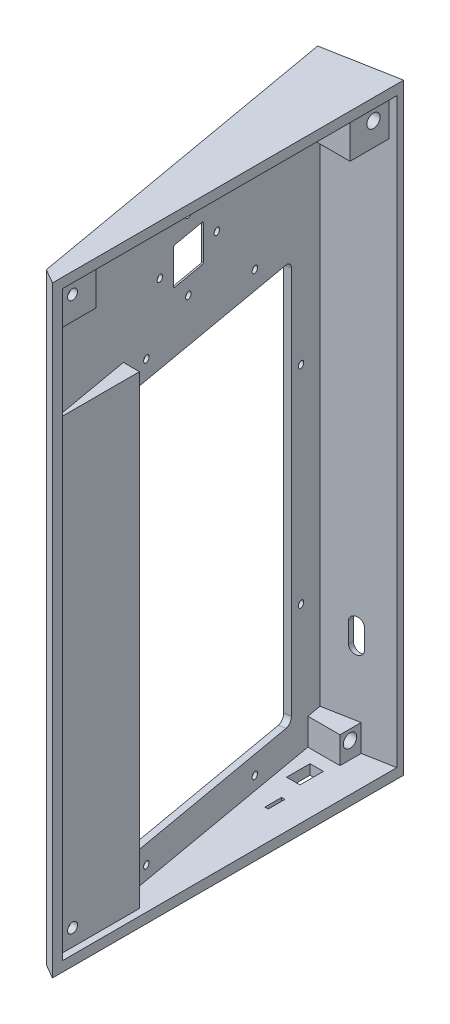
SolidWorks part; units mm, degrees
ref_plane "前视基准面" through (0, 0, 0) normal (0, 0, 1) x (1, 0, 0)
ref_plane "上视基准面" through (0, 0, 0) normal (0, 1, 0) x (1, 0, 0)
ref_plane "右视基准面" through (0, 0, 0) normal (1, 0, 0) x (0, 0, -1)
other "Configuration Table"
sketch "草图1" plane through (0, 0, 0) normal (0, 1, 0) x (1, 0, 0)
  line L0 (82.9035, -37.3993) -> (82.9035, -142.3993)
  line L1 (82.9035, -142.3993) -> (78.5734, -139.8993)
  line L2 (78.5734, -139.8993) -> (61.2086, -41.4185)
  line L3 (61.2086, -41.4185) -> (82.9035, -37.3993)
  dimension "D1" = 100
  dimension "D2" = 105
  dimension "D3" = 5
  dimension "D4" = 170
  dimension "D5" = 60
  dimension "D6" = 90.496
  dimension "D7" = 79.504
extrude "凸台-拉伸1" add sketch "草图1" along normal blind 180
sketch "草图5" plane through (52.2799, 0, -9.2184) normal (-0.9848, 0, 0.1736) x (0.1736, 0, 0.9848)
  line L0 (51.418, 180) -> (51.418, 0) construction
  line L1 (138.918, 12.5) -> (63.918, 12.5)
  line L2 (138.918, 12.5) -> (138.918, 132.5)
  line L3 (138.918, 132.5) -> (63.918, 132.5)
  line L4 (63.918, 12.5) -> (63.918, 132.5)
  line L5 (151.418, 180) -> (151.418, 0) construction
  line L6 (51.418, 0) -> (151.418, 0) construction
  dimension "D1" = 75
  dimension "D2" = 120
  dimension "D3" = 12.5
  dimension "D4" = 12.5
  dimension "D5" = 12.5
extrude "切除-拉伸2" cut sketch "草图5" against normal blind 2
sketch "草图7" plane through (82.9035, 0, 0) normal (1, 0, 0) x (0, 0, -1)
  line L8 (-139.3993, 3) -> (-40.3993, 3)
  line L9 (-40.3993, 3) -> (-40.3993, 177)
  line L10 (-40.3993, 177) -> (-139.3993, 177)
  line L11 (-139.3993, 177) -> (-139.3993, 3)
  line L12 (-139.3993, 3) -> (-40.3993, 3)
  line L13 (-40.3993, 3) -> (-40.3993, 177)
  line L14 (-40.3993, 177) -> (-139.3993, 177)
  line L15 (-139.3993, 177) -> (-139.3993, 3)
  dimension "D1" = 3
extrude "切除-拉伸3" cut sketch "草图7" against normal up to surface (19.8438 mm away) up to face at (71.8606, 72.5, 90.3116)
sketch "草图10" plane through (54.2496, 0, -9.5657) normal (0.9848, 0, -0.1736) x (-0.1736, 0, -0.9848)
  line L1 (-63.918, 12.5) -> (-60.418, 12.5) construction
  line L2 (-63.918, 12.5) -> (-63.918, 41.5) construction
  line L3 (-63.918, 41.5) -> (-60.418, 41.5) construction
  line L4 (-60.418, 12.5) -> (-60.418, 41.5) construction
  line L5 (-63.918, 132.5) -> (-60.418, 132.5) construction
  line L6 (-63.918, 132.5) -> (-63.918, 103.5) construction
  line L7 (-63.918, 103.5) -> (-60.418, 103.5) construction
  line L8 (-60.418, 132.5) -> (-60.418, 103.5) construction
  circle A0 centre (-60.418, 103.5) radius 1
  circle A1 centre (-60.418, 41.5) radius 1
  dimension "D1" = 29
  dimension "D2" = 29
  dimension "D3" = 3.5
  dimension "D4" = 3.5
extrude "切除-拉伸5" cut sketch "草图10" against normal blind 1
sketch "草图11" plane through (54.2496, 0, -9.5657) normal (0.9848, 0, -0.1736) x (-0.1736, 0, -0.9848)
  line L0 (-77.418, 7) -> (-117.418, 7) construction
  line L1 (-63.918, 132.5) -> (-77.418, 132.5) construction
  line L2 (-63.918, 132.5) -> (-63.918, 138) construction
  line L3 (-63.918, 138) -> (-77.418, 138) construction
  line L4 (-77.418, 132.5) -> (-77.418, 138) construction
  line L5 (-63.918, 12.5) -> (-77.418, 12.5) construction
  line L6 (-63.918, 12.5) -> (-63.918, 7) construction
  line L7 (-63.918, 7) -> (-77.418, 7) construction
  line L8 (-77.418, 12.5) -> (-77.418, 7) construction
  line L9 (-77.418, 138) -> (-117.418, 138) construction
  circle A0 centre (-117.418, 138) radius 1
  circle A1 centre (-77.418, 138) radius 1
  circle A2 centre (-117.418, 7) radius 1
  circle A3 centre (-77.418, 7) radius 1
  dimension "D1" = 13.5
  dimension "D2" = 5.5
  dimension "D3" = 13.5
  dimension "D4" = 5.5
  dimension "D5" = 40
  dimension "D6" = 40
extrude "切除-拉伸6" cut sketch "草图11" against normal blind 1
sketch "草图12" plane through (82.9035, 0, 0) normal (1, 0, 0) x (0, 0, -1)
  line L1 (-139.3993, 3) -> (-114.3993, 3)
  line L2 (-139.3993, 3) -> (-139.3993, 142)
  line L3 (-139.3993, 142) -> (-114.3993, 142)
  line L4 (-114.3993, 3) -> (-114.3993, 142)
  line L6 (-127.2419, 132.5) -> (-53.3813, 132.5) construction
  dimension "D1" = 9.5
  dimension "D2" = 25
extrude "凸台-拉伸3" add sketch "草图12" against normal up to surface (2.3874 mm away) up to face at (67.5194, 138, 65.6914)
sketch "草图13" plane through (54.2496, 0, -9.5657) normal (-0.9848, 0, 0.1736) x (0.1736, 0, 0.9848)
  line L4 (125.8773, 12.5) -> (138.918, 12.5)
  line L5 (138.918, 12.5) -> (138.918, 132.5)
  line L6 (138.918, 132.5) -> (125.8773, 132.5)
  line L7 (125.8773, 132.5) -> (125.8773, 12.5)
  line L8 (125.8773, 12.5) -> (138.918, 12.5)
  line L9 (138.918, 12.5) -> (138.918, 132.5)
  line L10 (138.918, 132.5) -> (125.8773, 132.5)
  line L11 (125.8773, 132.5) -> (125.8773, 12.5)
  dimension "D1" = 0
extrude "切除-拉伸7" cut sketch "草图13" against normal blind 2
sketch "草图14" plane through (52.2799, 0, -9.2184) normal (-0.9848, 0, 0.1736) x (0.1736, 0, 0.9848)
  line L0 (51.418, 180) -> (51.418, 0) construction
  line L1 (96.418, 150.5) -> (107.418, 150.5)
  line L2 (96.418, 150.5) -> (96.418, 161.5)
  line L3 (96.418, 161.5) -> (107.418, 161.5)
  line L4 (107.418, 150.5) -> (107.418, 161.5)
  line L5 (138.918, 132.5) -> (63.918, 132.5) construction
  line L6 (51.418, 180) -> (151.418, 180) construction
  dimension "D1" = 11
  dimension "D2" = 11
  dimension "D3" = 45
  dimension "D4" = 18
  dimension "D5" = 18.5
extrude "切除-拉伸8" cut sketch "草图14" against normal blind 2
chamfer "倒角1" distance 1.5 angle 60 4 edges at (70.9329, 156, 96.5677) (69.9778, 150.5, 91.1513) (69.9778, 161.5, 91.1513) (69.0228, 156, 85.7348) first distance on face at (71.9177, 156, 96.3941) first distance on face at (70.9626, 150.5, 90.9776) first distance on face at (70.9626, 161.5, 90.9776) first distance on face at (70.0076, 156, 85.5612)
fillet "圆角2" radius 0.5 4 edges at (72.6563, 150.5, 96.2638) (72.6563, 161.5, 96.2638) (70.7462, 161.5, 85.431) (70.7462, 150.5, 85.431)
sketch "草图17" plane through (9.4497, 0, 51.0074) normal (-0.1822, 0, -0.9833) x (-0.9833, 0, 0.1822)
  line L1 (-74.7037, 180) -> (-52.6396, 180)
  line L2 (-74.7037, 180) -> (-74.7037, 0)
  line L3 (-74.7037, 0) -> (-52.6396, 0)
  line L4 (-52.6396, 180) -> (-52.6396, 0)
extrude "凸台-拉伸9" add sketch "草图17" against normal blind 2
sketch "草图18" plane through (0, 0, 0) normal (0, -1, 0) x (1, 0, 0)
  line L0 (82.9035, 39.4333) -> (82.9035, 37.3993)
  line L1 (83.2679, 39.3658) -> (82.9035, 39.4333) construction
  line L2 (83.2679, 39.3658) -> (82.9035, 37.3993) construction
  line L3 (83.2679, 39.3658) -> (82.9035, 37.3993)
  line L4 (83.2679, 39.3658) -> (82.9035, 39.4333)
extrude "切除-拉伸9" cut sketch "草图18" against normal up to surface (180 mm away) up to face at (78.6267, 180, 73.3192)
sketch "草图19" plane through (0, 3, 0) normal (0, 1, 0) x (1, 0, 0)
  line L0 (82.9035, -40.3993) -> (82.9035, -36.7908) construction
  line L1 (77.596, -40.4166) -> (82.9035, -39.4333)
  line L2 (63.5225, -43.0238) -> (77.6894, -40.3993) construction
  line L3 (82.9035, -39.4333) -> (82.9035, -40.3993)
  line L4 (82.9035, -40.3993) -> (77.596, -40.4166)
extrude "切除-拉伸10" cut sketch "草图19" along normal up to surface (174 mm away) up to face at (77.507, 177, 80.5242)
sketch "草图20" plane through (82.9035, 0, 0) normal (1, 0, 0) x (0, 0, -1)
  line L1 (-139.3993, 142) -> (-114.3993, 142)
  line L2 (-139.3993, 142) -> (-139.3993, 3)
  line L3 (-139.3993, 3) -> (-114.3993, 3)
  line L4 (-114.3993, 142) -> (-114.3993, 3)
extrude "切除-拉伸11" cut sketch "草图20" against normal blind 2
sketch "草图21" plane through (54.2496, 0, -9.5657) normal (0.9848, 0, -0.1736) x (-0.1736, 0, -0.9848)
  line L0 (-107.418, 156) -> (-112.418, 156) construction
  line L1 (-107.418, 151) -> (-107.418, 161) construction
  line L2 (-101.918, 161.5) -> (-101.918, 166.5) construction
  line L3 (-106.918, 161.5) -> (-96.918, 161.5) construction
  line L4 (-96.418, 156) -> (-91.418, 156) construction
  line L5 (-96.418, 161) -> (-96.418, 151) construction
  line L6 (-101.918, 150.5) -> (-101.918, 145.5) construction
  line L7 (-96.918, 150.5) -> (-106.918, 150.5) construction
  circle A0 centre (-112.418, 156) radius 1
  circle A1 centre (-91.418, 156) radius 1
  circle A2 centre (-101.918, 145.5) radius 1
  circle A3 centre (-101.918, 166.5) radius 1
  dimension "D1" = 5
extrude "切除-拉伸12" cut sketch "草图21" against normal blind 1
sketch "草图23" plane through (80.9035, 0, 0) normal (1, 0, 0) x (0, 0, -1)
  line L0 (-51.4333, 8) -> (-51.4333, 26.4031) construction
  line L1 (-139.3993, 3) -> (-127.3993, 3)
  line L2 (-139.3993, 3) -> (-139.3993, 15)
  line L3 (-139.3993, 15) -> (-127.3993, 15)
  line L4 (-127.3993, 3) -> (-127.3993, 15)
  line L5 (-39.4333, 177) -> (-139.3993, 177) construction
  line L11 (-51.4333, 165) -> (-39.4333, 165)
  line L12 (-51.4333, 165) -> (-51.4333, 177)
  line L13 (-51.4333, 177) -> (-39.4333, 177)
  line L14 (-39.4333, 165) -> (-39.4333, 177)
  line L15 (-127.3993, 8) -> (-127.3993, 23.4787) construction
  line L17 (-127.3993, 165) -> (-139.3993, 165)
  line L18 (-127.3993, 165) -> (-127.3993, 177)
  line L19 (-127.3993, 177) -> (-139.3993, 177)
  line L20 (-139.3993, 165) -> (-139.3993, 177)
  dimension "D1" = 12
  dimension "D2" = 12
  dimension "D5" = 0
  dimension "D6" = 12
  dimension "D7" = 12
  dimension "D8" = 12
  dimension "D9" = 12
  dimension "D11" = 0
extrude "凸台-拉伸10" add sketch "草图23" against normal up to surface (0.3874 mm away) up to face at (73.5971, 156, 100.1597)
fillet "圆角4" radius 2 4 edges at (64.364, 132.5, 53.5549) (78.3724, 132.5, 127.2419) (64.364, 12.5, 53.5549) (78.3724, 12.5, 127.2419)
sketch "草图26" plane through (0, 177, 0) normal (0, 1, 0) x (1, 0, 0)
  line L3 (63.1752, -41.0542) -> (71.9242, -39.4333)
  line L4 (71.9242, -39.4333) -> (62.8894, -39.4333)
  line L5 (62.8894, -39.4333) -> (63.1752, -41.0542)
  line L6 (63.1752, -41.0542) -> (71.9242, -39.4333)
  line L7 (71.9242, -39.4333) -> (62.8894, -39.4333)
  line L8 (62.8894, -39.4333) -> (63.1752, -41.0542)
  dimension "D1" = 0
extrude "切除-拉伸15" cut sketch "草图26" against normal up to next
sketch "草图27" plane through (82.9035, 0, 0) normal (1, 0, 0) x (0, 0, -1)
  line L1 (-39.4333, 3) -> (-47.4333, 3)
  line L2 (-39.4333, 3) -> (-39.4333, 11)
  line L3 (-39.4333, 11) -> (-47.4333, 11)
  line L4 (-47.4333, 3) -> (-47.4333, 11)
  dimension "D1" = 8
  dimension "D2" = 8
extrude "凸台-拉伸11" add sketch "草图27" against normal up to surface (18.6035 mm away) up to face at (73.5971, 156, 100.1597)
sketch "草图28" plane through (82.9035, 0, 0) normal (1, 0, 0) x (0, 0, -1)
  line L1 (-47.4333, 3) -> (-39.4333, 3)
  line L2 (-47.4333, 3) -> (-47.4333, 11)
  line L3 (-47.4333, 11) -> (-39.4333, 11)
  line L4 (-39.4333, 3) -> (-39.4333, 11)
extrude "切除-拉伸16" cut sketch "草图28" against normal blind 9
sketch "草图29" plane through (0, 11, 0) normal (0, -1, 0) x (1, 0, 0)
  line L3 (73.9035, 41.1006) -> (73.9035, 39.4333)
  line L4 (73.9035, 39.4333) -> (82.9035, 39.4333)
  line L5 (82.9035, 39.4333) -> (73.9035, 41.1006)
  line L6 (73.9035, 41.1006) -> (73.9035, 39.4333)
  line L7 (73.9035, 39.4333) -> (82.9035, 39.4333)
  line L8 (82.9035, 39.4333) -> (73.9035, 41.1006)
  dimension "D1" = 0
extrude "凸台-拉伸12" add sketch "草图29" along normal up to surface (8 mm away) up to face at (76.9786, 3, 85.1663)
sketch "草图30" plane through (0, 3, 0) normal (0, -1, 0) x (1, 0, 0)
  line L3 (71.9242, 39.4333) -> (63.1752, 41.0542)
  line L4 (63.1752, 41.0542) -> (62.8894, 39.4333)
  line L5 (62.8894, 39.4333) -> (71.9242, 39.4333)
  line L6 (71.9242, 39.4333) -> (63.1752, 41.0542)
  line L7 (63.1752, 41.0542) -> (62.8894, 39.4333)
  line L8 (62.8894, 39.4333) -> (71.9242, 39.4333)
  dimension "D1" = 0
extrude "切除-拉伸17" cut sketch "草图30" against normal up to next
sketch "草图31" plane through (0, 0, 0) normal (0, -1, 0) x (1, 0, 0)
  line L1 (82.9035, 37.3993) -> (68.9035, 37.3993) construction
  line L2 (82.9035, 37.3993) -> (82.9035, 51.3993) construction
  line L3 (82.9035, 51.3993) -> (68.9035, 51.3993) construction
  line L4 (68.9035, 37.3993) -> (68.9035, 51.3993) construction
  line L5 (68.9035, 51.3993) -> (72.9035, 51.3993)
  line L6 (68.9035, 51.3993) -> (68.9035, 58.3993)
  line L7 (68.9035, 58.3993) -> (72.9035, 58.3993)
  line L8 (72.9035, 51.3993) -> (72.9035, 58.3993)
  dimension "D1" = 14
  dimension "D2" = 14
  dimension "D3" = 7
  dimension "D4" = 4
extrude "切除-拉伸18" cut sketch "草图31" against normal up to next
ref_plane "基准面1" through (0, 0, 37.3993) normal (0, 0, -1) x (-1, 0, 0)
ref_plane "基准面2" through (0, 0, 39.7193) normal (0, 0, -1) x (-1, 0, 0)
sketch "草图32" plane through (0, 0, 39.7193) normal (0, 0, -1) x (-1, 0, 0)
  line L0 (-72.7086, 36) -> (-72.7086, 30) construction
  line L1 (-70.7086, 36) -> (-70.7086, 30)
  line L2 (-74.7086, 36) -> (-74.7086, 30)
  line L3 (-82.9035, 180) -> (-61.2086, 180) construction
  line L4 (-61.2086, 180) -> (-61.2086, 0) construction
  arc A0 (-70.7086, 36) -> (-74.7086, 36) centre (-72.7086, 36) ccw
  arc A1 (-74.7086, 30) -> (-70.7086, 30) centre (-72.7086, 30) ccw
  point P2 (-72.7086, 33)
  point P9 (-72.7086, 28)
  point P10 (-72.7086, 38)
  dimension "D1" = 147
  dimension "D2" = 10
  dimension "D3" = 4
  dimension "D4" = 9.5
extrude "切除-拉伸23" cut sketch "草图32" against normal up to surface (1.9733 mm away) up to face at (75.3083, 89, 40.8404)
ref_plane "基准面4" through (0, 0, 40.2193) normal (0, 0, -1) x (-1, 0, 0)
sketch "草图35" plane through (0, 0, 40.2193) normal (0, 0, -1) x (-1, 0, 0)
  line L0 (-74.7086, 36) -> (-74.7086, 30) construction
  line L1 (-76.7086, 41) -> (-68.7086, 41)
  line L2 (-76.7086, 41) -> (-76.7086, 25)
  line L3 (-76.7086, 25) -> (-68.7086, 25)
  line L4 (-68.7086, 41) -> (-68.7086, 25)
  line L5 (-70.7086, 30) -> (-70.7086, 36) construction
  arc A0 (-70.7086, 36) -> (-74.7086, 36) centre (-72.7086, 36) ccw construction
  arc A1 (-74.7086, 30) -> (-70.7086, 30) centre (-72.7086, 30) ccw construction
  dimension "D1" = 5
  dimension "D2" = 5
  dimension "D3" = 2
  dimension "D4" = 2
extrude "切除-拉伸25" cut sketch "草图35" along normal up to surface (0.1902 mm away) up to face at (72.0561, 90, 39.4089)
fillet "圆角5" radius 0.5 4 edges at (76.7086, 25, 39.3831) (76.7086, 41, 39.3831) (68.7086, 25, 40.1241) (68.7086, 41, 40.1241)
sketch "草图36" plane through (0, 0, 0) normal (0, -1, 0) x (1, 0, 0)
  line L1 (82.9035, 37.3993) -> (74.4035, 37.3993) construction
  line L2 (82.9035, 37.3993) -> (82.9035, 64.3993) construction
  line L3 (82.9035, 64.3993) -> (74.4035, 64.3993) construction
  line L4 (74.4035, 37.3993) -> (74.4035, 64.3993) construction
  line L5 (74.4035, 64.3993) -> (73.4035, 64.3993)
  line L6 (74.4035, 64.3993) -> (74.4035, 69.3993)
  line L7 (74.4035, 69.3993) -> (73.4035, 69.3993)
  line L8 (73.4035, 64.3993) -> (73.4035, 69.3993)
  dimension "D1" = 8.5
  dimension "D2" = 27
  dimension "D3" = 1
  dimension "D4" = 5
extrude "切除-拉伸26" cut sketch "草图36" against normal up to next
sketch "草图37" plane through (0, 0, 0) normal (0, -1, 0) x (1, 0, 0)
  line L0 (73.4035, 66.8993) -> (74.4035, 66.8993) construction
  line L1 (73.4035, 69.3993) -> (73.4035, 64.3993) construction
  line L2 (74.4035, 64.3993) -> (74.4035, 69.3993) construction
  line L3 (73.9035, 64.3993) -> (73.9035, 69.3993) construction
  line L4 (73.4035, 64.3993) -> (74.4035, 64.3993) construction
  line L5 (74.4035, 69.3993) -> (73.4035, 69.3993) construction
  line L7 (74.9035, 69.8993) -> (72.9035, 69.8993)
  line L8 (74.9035, 69.8993) -> (74.9035, 63.8993)
  line L9 (74.9035, 63.8993) -> (72.9035, 63.8993)
  line L10 (72.9035, 69.8993) -> (72.9035, 63.8993)
  line L11 (74.9035, 69.8993) -> (72.9035, 63.8993) construction
  line L12 (74.9035, 63.8993) -> (72.9035, 69.8993) construction
  point P12 (73.9035, 66.8993)
  dimension "D1" = 6
  dimension "D2" = 2
extrude "切除-拉伸27" cut sketch "草图37" against normal blind 1
sketch "草图38" plane through (73.9035, 0, 0) normal (1, 0, 0) x (0, 0, -1)
  line L1 (-47.4333, 11) -> (-44.4333, 11) construction
  line L2 (-47.4333, 11) -> (-47.4333, 8) construction
  line L3 (-47.4333, 8) -> (-44.4333, 8) construction
  line L4 (-44.4333, 11) -> (-44.4333, 8) construction
  circle A0 centre (-44.4333, 8) radius 2
  dimension "D1" = 3
  dimension "D2" = 3
extrude "切除-拉伸28" cut sketch "草图38" against normal blind 3 contours A0
sketch "草图39" plane through (80.9035, 0, 0) normal (1, 0, 0) x (0, 0, -1)
  line L0 (-47.4333, 10.1358) -> (-47.4333, 2.8866) construction
  line L4 (-39.8038, 177) -> (-51.4333, 177) construction
  line L5 (-47.4333, 169) -> (-39.8038, 169) construction
  line L6 (-47.4333, 169) -> (-47.4333, 177) construction
  line L7 (-47.4333, 177) -> (-39.8038, 177) construction
  line L8 (-39.8038, 169) -> (-39.8038, 177) construction
  line L10 (-47.4333, 169) -> (-44.4333, 169) construction
  line L11 (-47.4333, 169) -> (-47.4333, 172) construction
  line L12 (-47.4333, 172) -> (-44.4333, 172) construction
  line L13 (-44.4333, 169) -> (-44.4333, 172) construction
  circle A0 centre (-44.4333, 172) radius 2
  dimension "D1" = 8
  dimension "D2" = 3
  dimension "D3" = 3
extrude "切除-拉伸30" cut sketch "草图39" against normal blind 3
sketch "草图40" plane through (80.9035, 0, 0) normal (1, 0, 0) x (0, 0, -1)
  line L1 (-127.3993, 177) -> (-131.3993, 177) construction
  line L2 (-127.3993, 177) -> (-127.3993, 171) construction
  line L3 (-127.3993, 171) -> (-131.3993, 171) construction
  line L4 (-131.3993, 177) -> (-131.3993, 171) construction
  line L5 (-131.3993, 171) -> (-134.3993, 171) construction
  line L6 (-131.3993, 171) -> (-131.3993, 172) construction
  line L7 (-131.3993, 172) -> (-134.3993, 172) construction
  line L8 (-134.3993, 171) -> (-134.3993, 172) construction
  line L9 (-139.3993, 3) -> (-134.3993, 3) construction
  line L10 (-139.3993, 3) -> (-139.3993, 8) construction
  line L11 (-139.3993, 8) -> (-134.3993, 8) construction
  line L12 (-134.3993, 3) -> (-134.3993, 8) construction
  circle A0 centre (-134.3993, 172) radius 1.5
  circle A1 centre (-134.3993, 8) radius 1.5
  dimension "D5" = 5
  dimension "D1" = 6
  dimension "D2" = 4
  dimension "D3" = 3
  dimension "D4" = 1
  dimension "D6" = 5
extrude "切除-拉伸31" cut sketch "草图40" against normal blind 2
